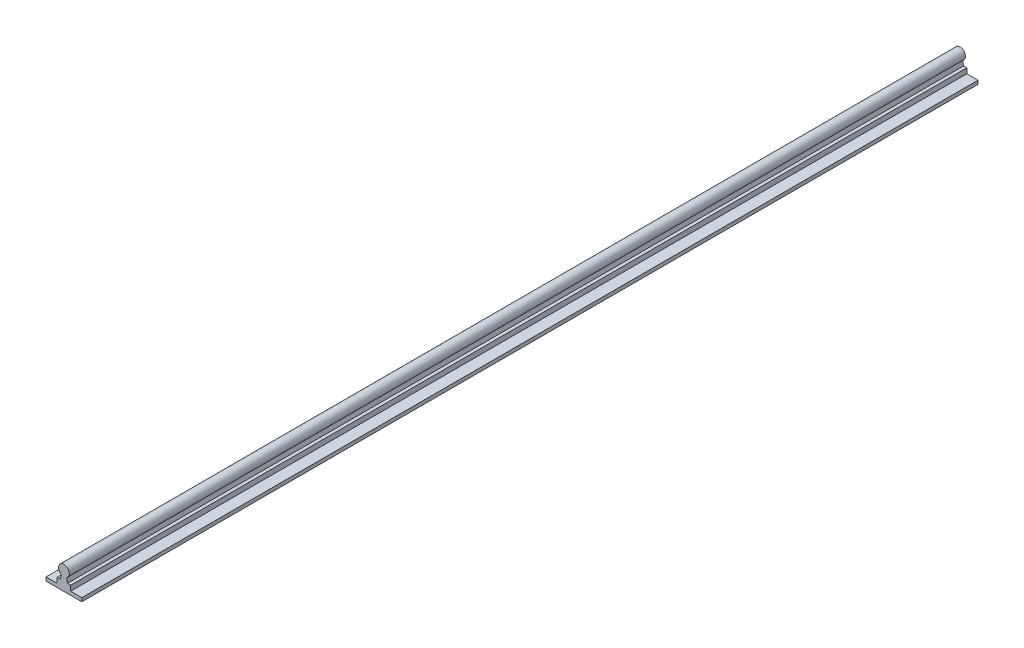
SolidWorks part; units mm, degrees
material "Chrome Stainless Steel"
ref_plane "Front Plane" through (0, 0, 0) normal (0, 0, 1) x (1, 0, 0)
ref_plane "Top Plane" through (0, 0, 0) normal (0, 1, 0) x (1, 0, 0)
ref_plane "Right Plane" through (0, 0, 0) normal (1, 0, 0) x (0, 0, -1)
sketch "Sketch1" plane through (0, 0, 0) normal (0, 0, 1) x (1, 0, 0)
  line L0 (24.3075, 0) -> (-15.6925, 0)
  line L1 (24.3075, 0) -> (24.3075, 4)
  line L2 (24.3075, 4) -> (11.8075, 4)
  line L3 (11.8075, 4) -> (11.8075, 9.8)
  line L4 (11.8075, 9.8) -> (8.2244, 9.8)
  line L5 (8.2244, 9.8) -> (7.3075, 15)
  line L6 (4.3075, 0) -> (4.3075, 36.0795) construction
  line L7 (0.3906, 9.8) -> (1.3075, 15)
  line L8 (-3.1925, 9.8) -> (0.3906, 9.8)
  line L9 (-3.1925, 4) -> (-3.1925, 9.8)
  line L10 (-15.6925, 0) -> (-15.6925, 4)
  line L11 (-15.6925, 4) -> (-3.1925, 4)
  arc A0 (7.3075, 15) -> (1.3075, 15) centre (4.3075, 20.1962) ccw
  point P17 (4.3075, 0)
  dimension "D5" = 6
  dimension "D1" = 20
  dimension "D2" = 4
  dimension "D3" = 9.8
  dimension "D4" = 15
  dimension "D6" = 3
  dimension "D8" = 20.1962
  dimension "D9" = 7.5
extrude "Boss-Extrude1" add sketch "Sketch1" along normal blind 1000
